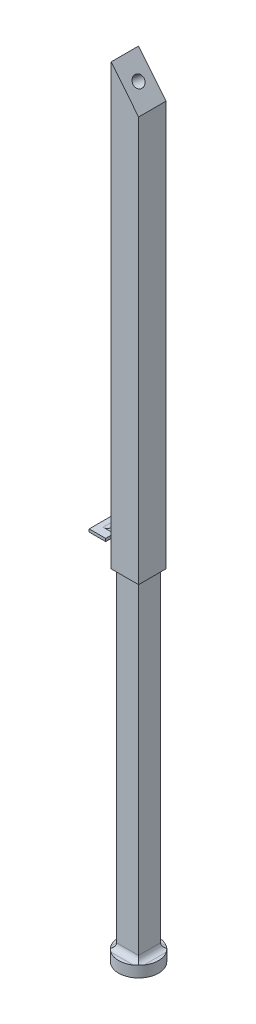
SolidWorks part; units mm, degrees
ref_plane "Ön Düzlem" through (0, 0, 0) normal (0, 0, 1) x (1, 0, 0)
ref_plane "Üst Düzlem" through (0, 0, 0) normal (0, 1, 0) x (1, 0, 0)
ref_plane "Sağ Düzlem" through (0, 0, 0) normal (1, 0, 0) x (0, 0, -1)
sketch "Çizim1" plane through (0, 0, 0) normal (0, 1, 0) x (1, 0, 0)
  line L1 (-12.5, 12.5) -> (12.5, 12.5)
  line L2 (-12.5, 12.5) -> (-12.5, -12.5)
  line L3 (-12.5, -12.5) -> (12.5, -12.5)
  line L4 (12.5, 12.5) -> (12.5, -12.5)
  line L5 (-12.5, 12.5) -> (12.5, -12.5) construction
  line L6 (-12.5, -12.5) -> (12.5, 12.5) construction
  point P0 (0, 0)
  dimension "D1" = 25
  dimension "D2" = 25
extrude "Yükseklik-Ekstrüzyon1" add sketch "Çizim1" along normal blind 400
sketch "Çizim2" plane through (0, 0, 0) normal (0, -1, 0) x (1, 0, 0)
  line L1 (-10, 10) -> (10, 10)
  line L2 (-10, 10) -> (-10, -10)
  line L3 (-10, -10) -> (10, -10)
  line L4 (10, 10) -> (10, -10)
  line L5 (-10, 10) -> (10, -10) construction
  line L6 (-10, -10) -> (10, 10) construction
  point P0 (0, 0)
  dimension "D1" = 20
  dimension "D2" = 20
extrude "Yükseklik-Ekstrüzyon2" add sketch "Çizim2" along normal blind 300
sketch "Çizim3" plane through (-12.5, 0, 0) normal (-1, 0, 0) x (0, 0, 1)
  circle A0 centre (0, 20.2349) radius 5
extrude "Yükseklik-Ekstrüzyon3" add sketch "Çizim3" along normal blind 5
sketch "Çizim4" plane through (-17.5, 0, 0) normal (-1, 0, 0) x (0, 0, 1)
  line L0 (12.5, 400) -> (12.5, 0) construction
  line L1 (-12.5, 18.9577) -> (12.5, 18.9577)
  line L2 (-12.5, 18.9577) -> (-12.5, 21.5121)
  line L3 (-12.5, 21.5121) -> (12.5, 21.5121)
  line L4 (12.5, 18.9577) -> (12.5, 21.5121)
  line L5 (-12.5, 18.9577) -> (12.5, 21.5121) construction
  line L6 (-12.5, 21.5121) -> (12.5, 18.9577) construction
  point P0 (0, 20.2349)
extrude "Yükseklik-Ekstrüzyon4" add sketch "Çizim4" along normal blind 15
fillet "Radyus1" radius 10 2 edges at (-17.5, 18.9577, 0) (-17.5, 21.5121, 0)
sketch "Çizim6" plane through (0, -300, 0) normal (0, -1, 0) x (1, 0, 0)
  circle A0 centre (0, 0) radius 18.1713
extrude "Yükseklik-Ekstrüzyon5" add sketch "Çizim6" along normal blind 10
fillet "Radyus2" radius 5 4 edges at (0, -300, -10) (-10, -300, 0) (0, -300, 10) (10, -300, 0)
sketch "Çizim7" plane through (0, 0, -12.5) normal (0, 0, -1) x (-1, 0, 0)
  line L0 (12.5, 400) -> (-29.2636, 348.2051)
  line L1 (-29.2636, 348.2051) -> (-29.2636, 417.1244)
  line L2 (-29.2636, 417.1244) -> (12.5, 417.1244)
  line L3 (12.5, 417.1244) -> (12.5, 400)
extrude "Kes-Ekstrüzyon2" cut sketch "Çizim7" against normal blind 58
sketch "Çizim8" plane through (187.8788, 151.4915, 0) normal (0.7785, 0.6277, 0) x (0, 0, -1)
  line L0 (12.5, 279.4021) -> (-12.5, 279.4021) construction
  circle A0 centre (0, 299.4021) radius 5
  dimension "D1" = 20
extrude "Kes-Ekstrüzyon3" cut sketch "Çizim8" against normal blind 32
